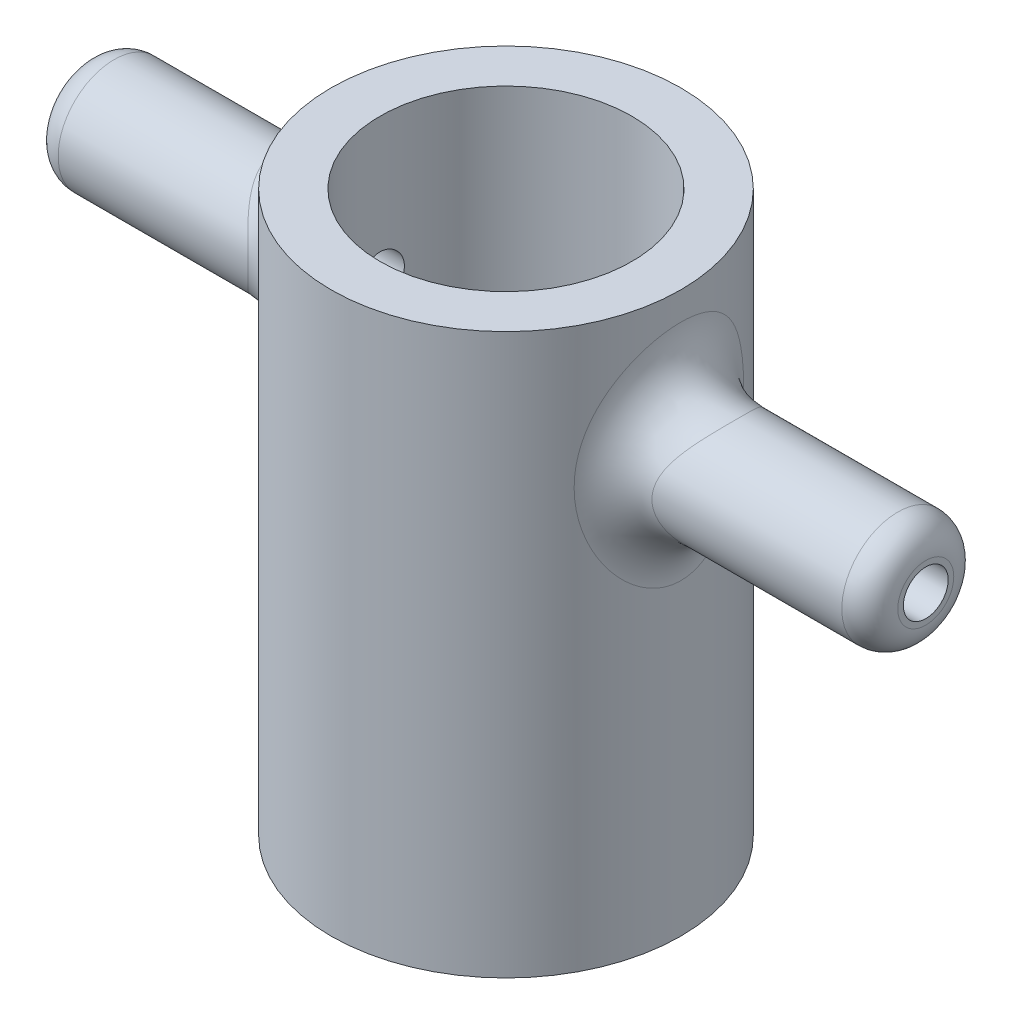
SolidWorks part; units mm, degrees
material "PET"
ref_plane "Спереди" through (0, 0, 0) normal (0, 0, 1) x (1, 0, 0)
ref_plane "Сверху" through (0, 0, 0) normal (0, 1, 0) x (1, 0, 0)
ref_plane "Справа" through (0, 0, 0) normal (1, 0, 0) x (0, 0, -1)
sketch "Эскиз1" plane through (0, 0, 0) normal (0, 1, 0) x (1, 0, 0)
  circle A0 centre (0, 0) radius 9
  circle A1 centre (0, 0) radius 12.5
  dimension "D1" = 18
  dimension "D2" = 25
extrude "Бобышка-Вытянуть3" add sketch "Эскиз1" along normal blind 40
sketch "Эскиз5" plane through (0, 0, 0) normal (1, 0, 0) x (0, 0, -1)
  line L0 (0, 0) -> (0, 30) construction
  circle A0 centre (0, 30) radius 4
  dimension "D1" = 8
  dimension "D2" = 30
extrude "Бобышка-Вытянуть5" add sketch "Эскиз5" along normal blind 30 and the other way blind 30
sketch "Эскиз6" plane through (-30, 0, 0) normal (-1, 0, 0) x (0, 0, 1)
  circle A0 centre (0, 30) radius 1.6
  dimension "D1" = 3.2
extrude "Вырез-Вытянуть1" cut sketch "Эскиз6" against normal through all both and the other way through all
sketch "Эскиз7" plane through (0, 40, 0) normal (0, 1, 0) x (1, 0, 0)
  circle A0 centre (0, 0) radius 9 construction
  circle A1 centre (0, 0) radius 9
extrude "Вырез-Вытянуть2" cut sketch "Эскиз7" against normal through all both and the other way through all
sketch "Эскиз8" plane through (0, 0, 0) normal (0, -1, 0) x (1, 0, 0)
  circle A0 centre (0, 0) radius 10.1
  dimension "D1" = 20.2
extrude "Вырез-Вытянуть3" cut sketch "Эскиз8" against normal blind 25
fillet "Скругление2" radius 2 2 edges at (-30, 30, -4) (30, 30, -4)
fillet "Скругление3" radius 4 2 edges at (-11.8635, 29.2989, 3.9381) (11.8635, 30.7011, 3.9381)
